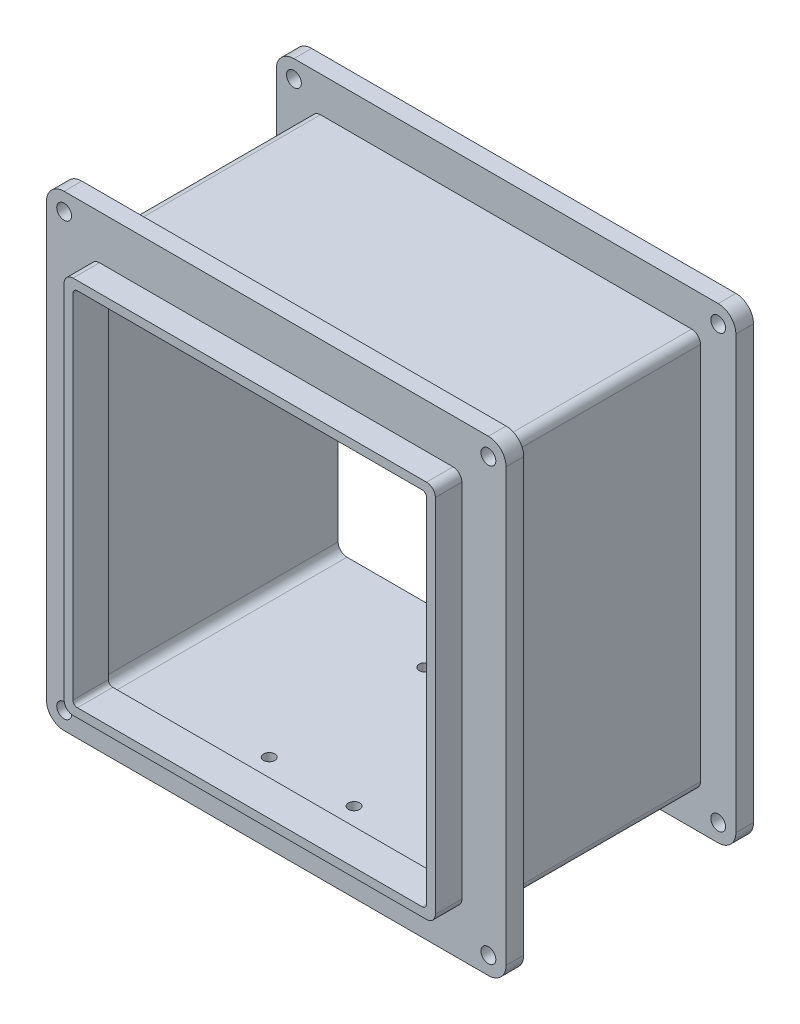
SolidWorks part; units mm, degrees
ref_plane "前视基准面" through (0, 0, 0) normal (0, 0, 1) x (1, 0, 0)
ref_plane "上视基准面" through (0, 0, 0) normal (0, 1, 0) x (1, 0, 0)
ref_plane "右视基准面" through (0, 0, 0) normal (1, 0, 0) x (0, 0, -1)
sketch "草图4" plane through (0, 0, 0) normal (0, 0, 1) x (1, 0, 0)
  line L1 (-105, -107.125) -> (105, -107.125)
  line L2 (-105, -107.125) -> (-105, 107.125)
  line L3 (-105, 107.125) -> (105, 107.125)
  line L4 (105, -107.125) -> (105, 107.125)
  line L5 (-105, -107.125) -> (105, 107.125) construction
  line L6 (-105, 107.125) -> (105, -107.125) construction
  line L7 (-110, -112.125) -> (110, -112.125)
  line L8 (-110, -112.125) -> (-110, 112.125)
  line L9 (-110, 112.125) -> (110, 112.125)
  line L10 (110, -112.125) -> (110, 112.125)
  line L11 (-110, -112.125) -> (110, 112.125) construction
  line L12 (-110, 112.125) -> (110, -112.125) construction
  point P0 (0, 0)
  point P6 (0, 0)
  dimension "D1" = 210
  dimension "D2" = 214.25
  dimension "D3" = 5
  dimension "D4" = 5
extrude "凸台-拉伸7" add sketch "草图4" along normal blind 120
sketch "草图7" plane through (0, 0, 0) normal (0, 0, -1) x (-1, 0, 0)
  line L0 (-110, 112.125) -> (110, 112.125) construction
  line L1 (130, 132.125) -> (-130, 132.125)
  line L2 (130, 132.125) -> (130, -132.125)
  line L3 (130, -132.125) -> (-130, -132.125)
  line L4 (-130, 132.125) -> (-130, -132.125)
  line L5 (130, 132.125) -> (-130, -132.125) construction
  line L6 (130, -132.125) -> (-130, 132.125) construction
  line L7 (-110, -112.125) -> (-110, 112.125) construction
  line L8 (105, -107.125) -> (-105, -107.125) construction
  line L9 (105, 107.125) -> (105, -107.125) construction
  line L10 (-105, 107.125) -> (105, 107.125) construction
  line L11 (-105, -107.125) -> (-105, 107.125) construction
  line L12 (105, -107.125) -> (-105, -107.125)
  line L13 (105, 107.125) -> (105, -107.125)
  line L14 (-105, 107.125) -> (105, 107.125)
  line L15 (-105, -107.125) -> (-105, 107.125)
  point P0 (0, 0)
  dimension "D1" = 20
  dimension "D2" = 20
extrude "凸台-拉伸8" add sketch "草图7" along normal blind 10
sketch "草图8" plane through (0, 0, 120) normal (0, 0, 1) x (1, 0, 0)
  line L1 (130, -132.125) -> (-130, -132.125)
  line L2 (130, -132.125) -> (130, 132.125)
  line L3 (130, 132.125) -> (-130, 132.125)
  line L4 (-130, -132.125) -> (-130, 132.125)
  line L5 (130, -132.125) -> (-130, 132.125) construction
  line L6 (130, 132.125) -> (-130, -132.125) construction
  line L7 (105, -107.125) -> (105, 107.125) construction
  line L8 (-105, -107.125) -> (105, -107.125) construction
  line L9 (-105, 107.125) -> (-105, -107.125) construction
  line L10 (105, 107.125) -> (-105, 107.125) construction
  line L11 (105, -107.125) -> (105, 107.125)
  line L12 (-105, -107.125) -> (105, -107.125)
  line L13 (-105, 107.125) -> (-105, -107.125)
  line L14 (105, 107.125) -> (-105, 107.125)
  point P0 (0, 0)
extrude "凸台-拉伸9" add sketch "草图8" along normal blind 10
fillet "圆角5" radius 5 8 edges at (-105, 107.125, 60) (-110, 112.125, 60) (105, -107.125, 60) (110, -112.125, 60) (-105, -107.125, 60) (-110, -112.125, 60) (110, 112.125, 60) (105, 107.125, 60)
fillet "圆角6" radius 10 8 edges at (130, 132.125, 125) (130, -132.125, 125) (-130, -132.125, 125) (-130, 132.125, 125) (-130, 132.125, -5) (-130, -132.125, -5) (130, -132.125, -5) (130, 132.125, -5)
hole_wizard "Ø8.4 (8.4) 直径孔1" positions "草图16" profile "草图17" hole size "Ø8.4" standard "GB" end condition through all
sketch "草图16" plane through (0, 0, -10) normal (0, 0, -1) x (-1, 0, 0)
  point P0 (120, -122.125)
  point P3 (120, 122.125)
  point P6 (-120, 122.125)
  point P9 (-120, -122.125)
sketch "草图17" plane through (-120, -122.125, -10) normal (1, 0, 0) x (0, 1, 0)
  line L0 (0, 0) -> (0, 140)
  line L1 (0, 140) -> (4.2, 140)
  line L2 (4.2, 140) -> (4.2, 0)
  line L5 (4.2, 0) -> (0, 0)
  line L11 (0, -6.35) -> (0, 107.95) construction
  dimension "通孔孔直径" = 8.4
  dimension "通孔孔深度" = 140
sketch "草图18" plane through (0, -112.125, 0) normal (0, -1, 0) x (1, 0, 0)
  line L0 (-120, 130) -> (120, 130) construction
  line L5 (105, 0) -> (105, 120) construction
  point P0 (-24, 110)
  point P1 (-24, 22)
  point P2 (24, 22)
  point P3 (24, 110)
  dimension "D1" = 48
  dimension "D2" = 48
  dimension "D3" = 88
  dimension "D4" = 88
  dimension "D5" = 100.2397
  dimension "D6" = 20
  dimension "D7" = 20
  dimension "D8" = 81
hole_wizard "Ø6.4 (6.4) 直径孔1" positions "草图21" profile "草图22" hole size "Ø6.4" standard "GB" end condition up to next
sketch "草图21" plane through (0, -112.125, 0) normal (0, -1, 0) x (-1, 0, 0)
  point P0 (24, -110)
  point P3 (-24, -110)
  point P6 (-24, -22)
  point P9 (24, -22)
sketch "草图22" plane through (-24, -112.125, 110) normal (1, 0, 0) x (0, 0, -1)
  line L0 (0, 0) -> (0, 5)
  line L1 (0, 5) -> (3.2, 5)
  line L2 (3.2, 5) -> (3.2, 0)
  line L5 (3.2, 0) -> (0, 0)
  line L11 (0, -6.35) -> (0, 107.95) construction
  dimension "通孔孔直径" = 6.4
  dimension "通孔孔深度" = 5
sketch "草图24" plane through (0, 0, 130) normal (0, 0, 1) x (1, 0, 0)
  line L0 (105, -102.125) -> (105, 102.125) construction
  line L1 (-100, -107.125) -> (100, -107.125) construction
  line L2 (-105, 102.125) -> (-105, -102.125) construction
  line L3 (100, 107.125) -> (-100, 107.125) construction
  line L4 (105, -102.125) -> (105, 102.125)
  line L5 (-100, -107.125) -> (100, -107.125)
  line L6 (-105, 102.125) -> (-105, -102.125)
  line L7 (100, 107.125) -> (-100, 107.125)
  line L9 (100, -102.125) -> (-100, -102.125)
  line L10 (100, -102.125) -> (100, 102.125)
  line L11 (100, 102.125) -> (-100, 102.125)
  line L12 (-100, -102.125) -> (-100, 102.125)
  line L13 (100, -102.125) -> (-100, 102.125) construction
  line L14 (100, 102.125) -> (-100, -102.125) construction
  arc A0 (105, 102.125) -> (100, 107.125) centre (100, 102.125) ccw construction
  arc A1 (100, -107.125) -> (105, -102.125) centre (100, -102.125) ccw construction
  arc A2 (-105, -102.125) -> (-100, -107.125) centre (-100, -102.125) ccw construction
  arc A3 (-100, 107.125) -> (-105, 102.125) centre (-100, 102.125) ccw construction
  arc A4 (105, 102.125) -> (100, 107.125) centre (100, 102.125) ccw
  arc A5 (100, -107.125) -> (105, -102.125) centre (100, -102.125) ccw
  arc A6 (-105, -102.125) -> (-100, -107.125) centre (-100, -102.125) ccw
  arc A7 (-100, 107.125) -> (-105, 102.125) centre (-100, 102.125) ccw
  point P12 (0, 0)
  dimension "D1" = 5
  dimension "D2" = 5
extrude "凸台-拉伸10" add sketch "草图24" along normal blind 15 separate body
sketch "草图25" plane through (0, 0, 130) normal (0, 0, -1) x (-1, 0, 0)
  line L0 (100, -102.125) -> (-100, -102.125) construction
  line L1 (-100, -102.125) -> (-100, 102.125) construction
  line L2 (100, 102.125) -> (100, -102.125) construction
  line L3 (-100, 102.125) -> (100, 102.125) construction
  line L4 (105, -102.125) -> (105, 102.125) construction
  line L5 (-100, -107.125) -> (100, -107.125) construction
  line L6 (-105, 102.125) -> (-105, -102.125) construction
  line L7 (100, 107.125) -> (-100, 107.125) construction
  line L8 (100, -102.125) -> (-100, -102.125)
  line L9 (-100, -102.125) -> (-100, 102.125)
  line L10 (100, 102.125) -> (100, -102.125)
  line L11 (-100, 102.125) -> (100, 102.125)
  line L12 (105, -102.125) -> (105, 102.125)
  line L13 (-100, -107.125) -> (100, -107.125)
  line L14 (-105, 102.125) -> (-105, -102.125)
  line L15 (100, 107.125) -> (-100, 107.125)
  arc A0 (105, 102.125) -> (100, 107.125) centre (100, 102.125) ccw construction
  arc A1 (100, -107.125) -> (105, -102.125) centre (100, -102.125) ccw construction
  arc A2 (-105, -102.125) -> (-100, -107.125) centre (-100, -102.125) ccw construction
  arc A3 (-100, 107.125) -> (-105, 102.125) centre (-100, 102.125) ccw construction
  arc A4 (105, 102.125) -> (100, 107.125) centre (100, 102.125) ccw
  arc A5 (100, -107.125) -> (105, -102.125) centre (100, -102.125) ccw
  arc A6 (-105, -102.125) -> (-100, -107.125) centre (-100, -102.125) ccw
  arc A7 (-100, 107.125) -> (-105, 102.125) centre (-100, 102.125) ccw
extrude "凸台-拉伸11" add sketch "草图25" along normal blind 5
fillet "圆角7" radius 2.5 12 edges at (103.5355, -105.6605, 125) (105, 0, 125) (103.5355, 105.6605, 125) (0, 107.125, 125) (-103.5355, 105.6605, 125) (-105, 0, 125) (-103.5355, -105.6605, 125) (0, -107.125, 125) (-100, -102.125, 135) (-100, 102.125, 135) (100, 102.125, 135) (100, -102.125, 135)
